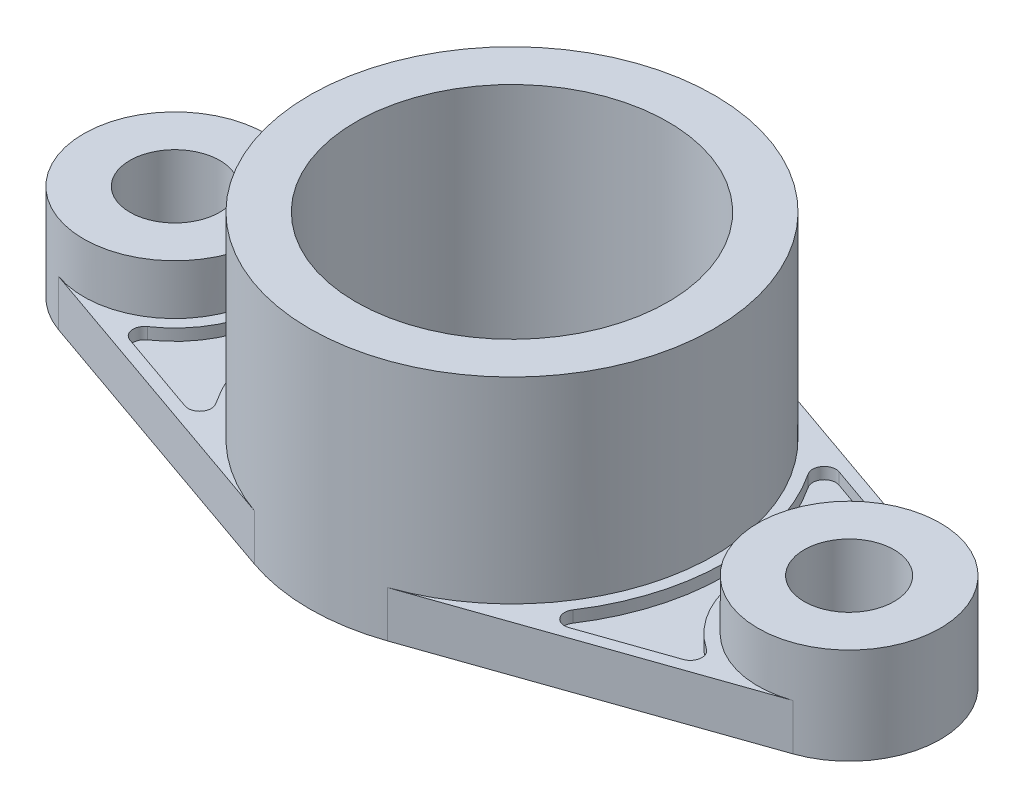
SolidWorks part; units mm, degrees
ref_plane "Front Plane" through (0, 0, 0) normal (0, 0, 1) x (1, 0, 0)
ref_plane "Top Plane" through (0, 0, 0) normal (0, 1, 0) x (1, 0, 0)
ref_plane "Right Plane" through (0, 0, 0) normal (1, 0, 0) x (0, 0, -1)
sketch "Sketch1" plane through (0, 0, 0) normal (0, 1, 0) x (1, 0, 0)
  line L0 (73.588, 0) -> (-73.588, 0) construction
  line L1 (0, 0) -> (0, 79.7842) construction
  line L2 (-95.2986, 22.3431) -> (-17.301, 49.5674)
  line L3 (-95.2986, -22.3431) -> (-17.301, -49.5674)
  line L4 (95.2986, -22.3431) -> (17.301, -49.5674)
  line L5 (95.2986, 22.3431) -> (17.301, 49.5674)
  line L6 (95.2986, -22.3431) -> (17.301, -49.5674)
  line L7 (95.2986, 22.3431) -> (17.301, 49.5674)
  circle A0 centre (0, 0) radius 52.5
  circle A1 centre (0, 0) radius 40.5
  circle A2 centre (-87.5, 0) radius 11.665
  circle A3 centre (-87.5, 0) radius 23.665
  circle A4 centre (87.5, 0) radius 23.665
  circle A5 centre (87.5, 0) radius 11.665
  dimension "D1" = 12
  dimension "D2" = 23.33
  dimension "D3" = 12
  dimension "D4" = 105
  dimension "D5" = 87.5
extrude "Boss-Extrude1" add sketch "Sketch1" along normal blind 12 contours A3 L3 A0 L2 | L4 A4 L5 A0 | A0 A1 | A4 A5 | A3 A2 region at (-58.0855, 0, 0) region at (-74.1858, 0, -18.7492) region at (0, 0, -51.0151) region at (58.0855, 0, 0) region at (106.2492, 0, -13.3142)
extrude "Boss-Extrude2" add sketch "Sketch1<3>" along normal blind 25 contours A3 A2 | A4 A5 | A0 A1 region at (-74.1858, 0, -18.7492) region at (0, 0, -51.0151) region at (106.2492, 0, -13.3142)
sketch "Sketch1<3>" plane through (0, 0, 0) normal (0, 1, 0) x (1, 0, 0) same geometry as "Sketch1"
extrude "Boss-Extrude3" add sketch "Sketch1<4>" along normal blind 63 contours A0 A1 region at (0, 0, -51.0151)
sketch "Sketch1<4>" plane through (0, 0, 0) normal (0, 1, 0) x (1, 0, 0) same geometry as "Sketch1"
sketch "Sketch2" plane through (0, 12, 0) normal (0, 1, 0) x (1, 0, 0)
  line L0 (-78.3996, -25.064) -> (-40.0101, -38.4635)
  line L1 (-40.0101, 38.4635) -> (-78.3996, 25.064)
  line L2 (-95.2986, -22.3431) -> (-17.301, -49.5674)
  line L3 (-17.301, 49.5674) -> (-95.2986, 22.3431)
  line L4 (-95.2986, -22.3431) -> (-17.301, -49.5674)
  line L5 (-17.301, 49.5674) -> (-95.2986, 22.3431)
  line L6 (95.2986, 22.3431) -> (17.301, 49.5674)
  line L7 (17.301, -49.5674) -> (95.2986, -22.3431)
  line L8 (95.2986, 22.3431) -> (17.301, 49.5674)
  line L9 (17.301, -49.5674) -> (95.2986, -22.3431)
  line L10 (78.3996, 25.064) -> (40.0101, 38.4635)
  line L11 (40.0101, -38.4635) -> (78.3996, -25.064)
  arc A0 (-40.0101, 38.4635) -> (-40.0101, -38.4635) centre (0, 0) ccw
  arc A1 (-78.3996, -25.064) -> (-78.3996, 25.064) centre (-87.5, 0) ccw
  arc A2 (-17.301, 49.5674) -> (-17.301, -49.5674) centre (0, 0) ccw
  arc A3 (-95.2986, -22.3431) -> (-95.2986, 22.3431) centre (-87.5, 0) ccw
  arc A4 (-17.301, 49.5674) -> (-17.301, -49.5674) centre (0, 0) ccw
  arc A5 (-95.2986, -22.3431) -> (-95.2986, 22.3431) centre (-87.5, 0) ccw
  arc A6 (17.301, -49.5674) -> (17.301, 49.5674) centre (0, 0) ccw
  arc A7 (95.2986, 22.3431) -> (95.2986, -22.3431) centre (87.5, 0) ccw
  arc A8 (17.301, -49.5674) -> (17.301, 49.5674) centre (0, 0) ccw
  arc A9 (95.2986, 22.3431) -> (95.2986, -22.3431) centre (87.5, 0) ccw
  arc A10 (40.0101, -38.4635) -> (40.0101, 38.4635) centre (0, 0) ccw
  arc A11 (78.3996, 25.064) -> (78.3996, -25.064) centre (87.5, 0) ccw
  dimension "D1" = 0
  dimension "D2" = 0
  dimension "D3" = 3
extrude "Cut-Extrude1" cut sketch "Sketch2" against normal blind 3 contours L0 A0 L1 A1 | L10 A10 L11 A11
fillet "Fillet1" radius 3 4 edges at (-78.3996, 10.5, -25.064) (-78.3996, 10.5, 25.064) (-40.0101, 10.5, 38.4635) (-40.0101, 10.5, -38.4635)
fillet "Fillet2" radius 3 4 edges at (78.3996, 10.5, 25.064) (78.3996, 10.5, -25.064) (40.0101, 10.5, -38.4635) (40.0101, 10.5, 38.4635)
